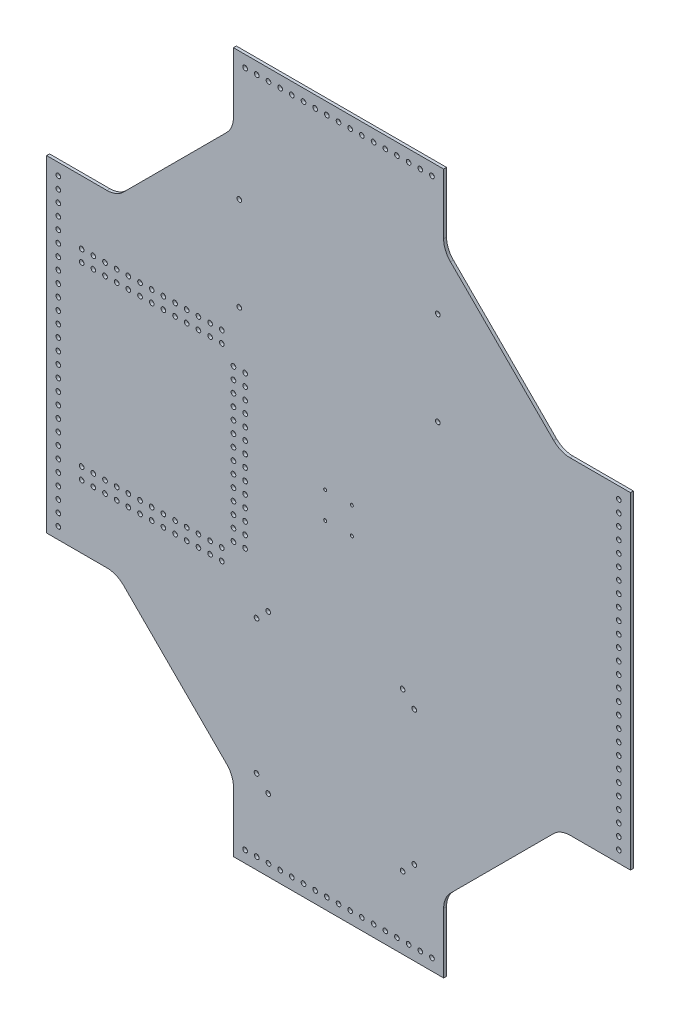
SolidWorks part; units mm, degrees
material "1060 Alloy"
ref_plane "Front Plane" through (0, 0, 0) normal (0, 0, 1) x (1, 0, 0)
ref_plane "Top Plane" through (0, 0, 0) normal (0, 1, 0) x (1, 0, 0)
ref_plane "Right Plane" through (0, 0, 0) normal (1, 0, 0) x (0, 0, -1)
sketch "Sketch1" plane through (0, 0, 0) normal (0, 0, 1) x (1, 0, 0)
  line L0 (-317.5, 177.8) -> (-317.5, -177.8)
  line L1 (-317.5, 381) -> (317.5, 381)
  line L2 (-317.5, 381) -> (-317.5, -381)
  line L3 (-317.5, -381) -> (317.5, -381)
  line L4 (317.5, 381) -> (317.5, -381)
  line L5 (-317.5, 381) -> (317.5, -381) construction
  line L6 (-317.5, -381) -> (317.5, 381) construction
  line L7 (317.5, 177.8) -> (317.5, -177.8)
  line L8 (-114.3, 381) -> (114.3, 381)
  line L9 (-114.3, -381) -> (114.3, -381)
  line L10 (-317.5, -177.8) -> (-241.3, -177.8)
  line L11 (-317.5, 177.8) -> (-241.3, 177.8)
  line L12 (-114.3, 381) -> (-114.3, 304.8)
  line L13 (114.3, 381) -> (114.3, 304.8)
  line L14 (317.5, 177.8) -> (241.3, 177.8)
  line L15 (317.5, -177.8) -> (241.3, -177.8)
  line L16 (114.3, -381) -> (114.3, -304.8)
  line L17 (-114.3, -381) -> (-114.3, -304.8)
  line L18 (-241.3, 177.8) -> (-114.3, 304.8)
  line L19 (114.3, 304.8) -> (241.3, 177.8)
  line L20 (114.3, -304.8) -> (241.3, -177.8)
  line L21 (-114.3, -304.8) -> (-241.3, -177.8)
  point P0 (0, 0)
  point P9 (-317.5, 0)
  point P12 (317.5, 0)
  point P15 (0, 381)
  point P18 (0, -381)
  dimension "D1" = 635
  dimension "D2" = 762
  dimension "D3" = 355.6
  dimension "D4" = 228.6
  dimension "D5" = 228.6
  dimension "D6" = 76.2
  dimension "D7" = 76.2
  dimension "D8" = 76.2
  dimension "D9" = 76.2
  dimension "D10" = 76.2
  dimension "D11" = 76.2
  dimension "D12" = 76.2
  dimension "D13" = 76.2
extrude "Boss-Extrude1" add sketch "Sketch1" along normal blind 3.175 contours L21 L17 L3 L16 L20 L15 L4 L14 L19 L13 L1 L12 L18 L11 L0 L10 region at (0, 0, 0)
sketch "Sketch2" plane through (0, 0, 3.175) normal (0, 0, 1) x (1, 0, 0)
  line L0 (-317.5, 177.8) -> (-317.5, -177.8) construction
  line L1 (-317.5, 177.8) -> (-241.3, 177.8) construction
  line L2 (-304.8, 177.8) -> (-304.8, -177.8) construction
  line L3 (-317.5, -177.8) -> (-241.3, -177.8) construction
  line L4 (0, 381) -> (0, -381) construction
  line L5 (-114.3, 381) -> (114.3, 381) construction
  line L6 (-114.3, -381) -> (114.3, -381) construction
  line L7 (-317.5, 0) -> (317.5, 0) construction
  line L8 (317.5, 177.8) -> (317.5, -177.8) construction
  line L9 (-114.3, -381) -> (-114.3, -304.8) construction
  line L10 (-114.3, -368.3) -> (114.3, -368.3) construction
  line L11 (114.3, -381) -> (114.3, -304.8) construction
  line L12 (-304.8, 165.1) -> (-292.1, 165.1) construction
  line L13 (-292.1, 165.1) -> (-292.1, -177.8) construction
  line L14 (317.5, 165.1) -> (272.8241, 165.1) construction
  line L15 (292.1, 177.8) -> (292.1, -177.8) construction
  line L16 (317.5, 177.8) -> (241.3, 177.8) construction
  line L17 (317.5, -177.8) -> (241.3, -177.8) construction
  line L18 (279.4, 177.8) -> (279.4, -177.8) construction
  line L19 (-101.6, -381) -> (-101.6, -331.9568) construction
  line L20 (-114.3, -342.9) -> (114.3, -342.9) construction
  line L21 (-114.3, -355.6) -> (114.3, -355.6) construction
  line L22 (-101.6, 381) -> (-101.6, 343.8859) construction
  line L23 (-114.3, 342.9) -> (114.3, 342.9) construction
  line L24 (-114.3, 381) -> (-114.3, 304.8) construction
  line L25 (114.3, 381) -> (114.3, 304.8) construction
  line L26 (-114.3, 355.6) -> (114.3, 355.6) construction
  circle A0 centre (-304.8, 165.1) radius 2.54
  circle A1 centre (-304.8, 152.4) radius 2.54
  circle A2 centre (-304.8, 139.7) radius 2.54
  circle A3 centre (-304.8, 127) radius 2.54
  circle A4 centre (-304.8, 114.3) radius 2.54
  circle A5 centre (-304.8, 101.6) radius 2.54
  circle A6 centre (-304.8, 88.9) radius 2.54
  circle A7 centre (-304.8, 76.2) radius 2.54
  circle A8 centre (-304.8, 63.5) radius 2.54
  circle A9 centre (-304.8, 50.8) radius 2.54
  circle A10 centre (-304.8, 38.1) radius 2.54
  circle A11 centre (-304.8, 25.4) radius 2.54
  circle A12 centre (-304.8, 12.7) radius 2.54
  circle A13 centre (-304.8, 0) radius 2.54
  circle A14 centre (-304.8, -12.7) radius 2.54
  circle A15 centre (-304.8, -25.4) radius 2.54
  circle A16 centre (-304.8, -38.1) radius 2.54
  circle A17 centre (-304.8, -50.8) radius 2.54
  circle A18 centre (-304.8, -63.5) radius 2.54
  circle A19 centre (-304.8, -76.2) radius 2.54
  circle A20 centre (-304.8, -88.9) radius 2.54
  circle A21 centre (-304.8, -101.6) radius 2.54
  circle A22 centre (-304.8, -114.3) radius 2.54
  circle A23 centre (-304.8, -127) radius 2.54
  circle A24 centre (-304.8, -139.7) radius 2.54
  circle A25 centre (-304.8, -152.4) radius 2.54
  circle A26 centre (-304.8, -165.1) radius 2.54
  circle A27 centre (304.8, -165.1) radius 2.54
  circle A28 centre (304.8, -152.4) radius 2.54
  circle A29 centre (304.8, -139.7) radius 2.54
  circle A30 centre (304.8, -127) radius 2.54
  circle A31 centre (304.8, -114.3) radius 2.54
  circle A32 centre (304.8, -101.6) radius 2.54
  circle A33 centre (304.8, -88.9) radius 2.54
  circle A34 centre (304.8, -76.2) radius 2.54
  circle A35 centre (304.8, -63.5) radius 2.54
  circle A36 centre (304.8, -50.8) radius 2.54
  circle A37 centre (304.8, -38.1) radius 2.54
  circle A38 centre (304.8, -25.4) radius 2.54
  circle A39 centre (304.8, -12.7) radius 2.54
  circle A40 centre (304.8, 0) radius 2.54
  circle A41 centre (304.8, 12.7) radius 2.54
  circle A42 centre (304.8, 25.4) radius 2.54
  circle A43 centre (304.8, 38.1) radius 2.54
  circle A44 centre (304.8, 50.8) radius 2.54
  circle A45 centre (304.8, 63.5) radius 2.54
  circle A46 centre (304.8, 76.2) radius 2.54
  circle A47 centre (304.8, 88.9) radius 2.54
  circle A48 centre (304.8, 101.6) radius 2.54
  circle A49 centre (304.8, 114.3) radius 2.54
  circle A50 centre (304.8, 127) radius 2.54
  circle A51 centre (304.8, 139.7) radius 2.54
  circle A52 centre (304.8, 152.4) radius 2.54
  circle A53 centre (304.8, 165.1) radius 2.54
  circle A54 centre (-101.6, -368.3) radius 2.54
  circle A55 centre (-88.9, -368.3) radius 2.54
  circle A56 centre (-76.2, -368.3) radius 2.54
  circle A57 centre (-63.5, -368.3) radius 2.54
  circle A58 centre (-50.8, -368.3) radius 2.54
  circle A59 centre (-38.1, -368.3) radius 2.54
  circle A60 centre (-25.4, -368.3) radius 2.54
  circle A61 centre (-12.7, -368.3) radius 2.54
  circle A62 centre (0, -368.3) radius 2.54
  circle A63 centre (12.7, -368.3) radius 2.54
  circle A64 centre (25.4, -368.3) radius 2.54
  circle A65 centre (38.1, -368.3) radius 2.54
  circle A66 centre (50.8, -368.3) radius 2.54
  circle A67 centre (63.5, -368.3) radius 2.54
  circle A68 centre (76.2, -368.3) radius 2.54
  circle A69 centre (88.9, -368.3) radius 2.54
  circle A70 centre (101.6, -368.3) radius 2.54
  circle A71 centre (101.6, 368.3) radius 2.54
  circle A72 centre (88.9, 368.3) radius 2.54
  circle A73 centre (76.2, 368.3) radius 2.54
  circle A74 centre (63.5, 368.3) radius 2.54
  circle A75 centre (50.8, 368.3) radius 2.54
  circle A76 centre (38.1, 368.3) radius 2.54
  circle A77 centre (25.4, 368.3) radius 2.54
  circle A78 centre (12.7, 368.3) radius 2.54
  circle A79 centre (0, 368.3) radius 2.54
  circle A80 centre (-12.7, 368.3) radius 2.54
  circle A81 centre (-25.4, 368.3) radius 2.54
  circle A82 centre (-38.1, 368.3) radius 2.54
  circle A83 centre (-50.8, 368.3) radius 2.54
  circle A84 centre (-63.5, 368.3) radius 2.54
  circle A85 centre (-76.2, 368.3) radius 2.54
  circle A86 centre (-88.9, 368.3) radius 2.54
  circle A87 centre (-101.6, 368.3) radius 2.54
  circle A115 centre (292.1, 165.1) radius 2.54
  circle A116 centre (279.4, 165.1) radius 2.54
  circle A117 centre (279.4, 152.4) radius 2.54
  circle A118 centre (292.1, 152.4) radius 2.54
  circle A119 centre (279.4, 139.7) radius 2.54
  circle A120 centre (292.1, 139.7) radius 2.54
  circle A121 centre (279.4, 127) radius 2.54
  circle A122 centre (292.1, 127) radius 2.54
  circle A123 centre (279.4, 114.3) radius 2.54
  circle A124 centre (292.1, 114.3) radius 2.54
  circle A125 centre (279.4, 101.6) radius 2.54
  circle A126 centre (292.1, 101.6) radius 2.54
  circle A127 centre (279.4, 88.9) radius 2.54
  circle A128 centre (292.1, 88.9) radius 2.54
  circle A129 centre (279.4, 76.2) radius 2.54
  circle A130 centre (292.1, 76.2) radius 2.54
  circle A131 centre (279.4, 63.5) radius 2.54
  circle A132 centre (292.1, 63.5) radius 2.54
  circle A133 centre (279.4, 50.8) radius 2.54
  circle A134 centre (292.1, 50.8) radius 2.54
  circle A135 centre (279.4, 38.1) radius 2.54
  circle A136 centre (292.1, 38.1) radius 2.54
  circle A137 centre (279.4, 25.4) radius 2.54
  circle A138 centre (292.1, 25.4) radius 2.54
  circle A139 centre (279.4, 12.7) radius 2.54
  circle A140 centre (292.1, 12.7) radius 2.54
  circle A141 centre (279.4, 0) radius 2.54
  circle A142 centre (292.1, 0) radius 2.54
  circle A143 centre (279.4, -12.7) radius 2.54
  circle A144 centre (292.1, -12.7) radius 2.54
  circle A145 centre (279.4, -25.4) radius 2.54
  circle A146 centre (292.1, -25.4) radius 2.54
  circle A147 centre (279.4, -38.1) radius 2.54
  circle A148 centre (292.1, -38.1) radius 2.54
  circle A149 centre (279.4, -50.8) radius 2.54
  circle A150 centre (292.1, -50.8) radius 2.54
  circle A151 centre (279.4, -63.5) radius 2.54
  circle A152 centre (292.1, -63.5) radius 2.54
  circle A153 centre (279.4, -76.2) radius 2.54
  circle A154 centre (292.1, -76.2) radius 2.54
  circle A155 centre (279.4, -88.9) radius 2.54
  circle A156 centre (292.1, -88.9) radius 2.54
  circle A157 centre (279.4, -101.6) radius 2.54
  circle A158 centre (292.1, -101.6) radius 2.54
  circle A159 centre (279.4, -114.3) radius 2.54
  circle A160 centre (292.1, -114.3) radius 2.54
  circle A161 centre (279.4, -127) radius 2.54
  circle A162 centre (292.1, -127) radius 2.54
  circle A163 centre (279.4, -139.7) radius 2.54
  circle A164 centre (292.1, -139.7) radius 2.54
  circle A165 centre (279.4, -152.4) radius 2.54
  circle A166 centre (292.1, -152.4) radius 2.54
  circle A167 centre (279.4, -165.1) radius 2.54
  circle A168 centre (292.1, -165.1) radius 2.54
  circle A169 centre (-101.6, -355.6) radius 2.54
  circle A170 centre (-101.6, -342.9) radius 2.54
  circle A171 centre (-88.9, -342.9) radius 2.54
  circle A172 centre (-88.9, -355.6) radius 2.54
  circle A173 centre (-76.2, -342.9) radius 2.54
  circle A174 centre (-76.2, -355.6) radius 2.54
  circle A175 centre (-63.5, -342.9) radius 2.54
  circle A176 centre (-63.5, -355.6) radius 2.54
  circle A177 centre (-50.8, -342.9) radius 2.54
  circle A178 centre (-50.8, -355.6) radius 2.54
  circle A179 centre (-38.1, -342.9) radius 2.54
  circle A180 centre (-38.1, -355.6) radius 2.54
  circle A181 centre (-25.4, -342.9) radius 2.54
  circle A182 centre (-25.4, -355.6) radius 2.54
  circle A183 centre (-12.7, -342.9) radius 2.54
  circle A184 centre (-12.7, -355.6) radius 2.54
  circle A185 centre (0, -342.9) radius 2.54
  circle A186 centre (0, -355.6) radius 2.54
  circle A187 centre (12.7, -342.9) radius 2.54
  circle A188 centre (12.7, -355.6) radius 2.54
  circle A189 centre (25.4, -342.9) radius 2.54
  circle A190 centre (25.4, -355.6) radius 2.54
  circle A191 centre (38.1, -342.9) radius 2.54
  circle A192 centre (38.1, -355.6) radius 2.54
  circle A193 centre (50.8, -342.9) radius 2.54
  circle A194 centre (50.8, -355.6) radius 2.54
  circle A195 centre (63.5, -342.9) radius 2.54
  circle A196 centre (63.5, -355.6) radius 2.54
  circle A197 centre (76.2, -342.9) radius 2.54
  circle A198 centre (76.2, -355.6) radius 2.54
  circle A199 centre (88.9, -342.9) radius 2.54
  circle A200 centre (88.9, -355.6) radius 2.54
  circle A201 centre (101.6, -342.9) radius 2.54
  circle A202 centre (101.6, -355.6) radius 2.54
  circle A203 centre (-101.6, 355.6) radius 2.54
  circle A204 centre (-101.6, 342.9) radius 2.54
  circle A205 centre (-88.9, 342.9) radius 2.54
  circle A206 centre (-88.9, 355.6) radius 2.54
  circle A207 centre (-76.2, 342.9) radius 2.54
  circle A208 centre (-76.2, 355.6) radius 2.54
  circle A209 centre (-63.5, 342.9) radius 2.54
  circle A210 centre (-63.5, 355.6) radius 2.54
  circle A211 centre (-50.8, 342.9) radius 2.54
  circle A212 centre (-50.8, 355.6) radius 2.54
  circle A213 centre (-38.1, 342.9) radius 2.54
  circle A214 centre (-38.1, 355.6) radius 2.54
  circle A215 centre (-25.4, 342.9) radius 2.54
  circle A216 centre (-25.4, 355.6) radius 2.54
  circle A217 centre (-12.7, 342.9) radius 2.54
  circle A218 centre (-12.7, 355.6) radius 2.54
  circle A219 centre (0, 342.9) radius 2.54
  circle A220 centre (0, 355.6) radius 2.54
  circle A221 centre (12.7, 342.9) radius 2.54
  circle A222 centre (12.7, 355.6) radius 2.54
  circle A223 centre (25.4, 342.9) radius 2.54
  circle A224 centre (25.4, 355.6) radius 2.54
  circle A225 centre (38.1, 342.9) radius 2.54
  circle A226 centre (38.1, 355.6) radius 2.54
  circle A227 centre (50.8, 342.9) radius 2.54
  circle A228 centre (50.8, 355.6) radius 2.54
  circle A229 centre (63.5, 342.9) radius 2.54
  circle A230 centre (63.5, 355.6) radius 2.54
  circle A231 centre (76.2, 342.9) radius 2.54
  circle A232 centre (76.2, 355.6) radius 2.54
  circle A233 centre (88.9, 342.9) radius 2.54
  circle A234 centre (88.9, 355.6) radius 2.54
  circle A235 centre (101.6, 342.9) radius 2.54
  circle A236 centre (101.6, 355.6) radius 2.54
  dimension "D1" = 5.08
  dimension "D5" = 5.08
  dimension "D2" = 12.7
  dimension "D3" = 12.7
  dimension "D6" = 12.7
  dimension "D7" = 12.7
  dimension "D9" = 12.7
  dimension "D4" = 27
  dimension "D8" = 17
  dimension "D11" = 3
  dimension "D12" = 27
  dimension "D13" = 3
  dimension "D14" = 17
  dimension "D15" = 3
  dimension "D16" = 17
extrude "Cut-Extrude2" cut sketch "Sketch2" against normal blind 3.175 contours A87 | A86 | A85 | A84 | A83 | A82 | A80 | A81 | A79 | A78 | A77 | A76 | A75 | A74 | A73 | A72 | A71 | A53 | A52 | A51 | A50 | A49 | A48 | A47 | A46 | A45 | A44 | A43 | A42 | A41 | A40 | A39 | A38 | A37 | A36 | A35 | A34 | A33 | A32 | A31 | A30 | A29 | A28 | A27 | A70 | A69 | A68 | A67 | A66 | A65 | A64 | A63 | A62 | A61 | A60 | A59 | A58 | A56 | A57 | A55 | A54 | A26 | A25 | A24 | A23 | A22 | A21 | A20 | A19 | A18 | A17 | A16 | A15 | A14 | A13 | A12 | A11 | A10 | A9 | A8 | A7 | A0 | A1 | A2 | A3 | A4 | A5 | A6
sketch "Sketch3" plane through (0, 0, 3.175) normal (0, 0, 1) x (1, 0, 0)
  line L0 (-317.5, 177.8) -> (-317.5, -177.8) construction
  line L1 (-14.478, 14.478) -> (14.478, 14.478)
  line L2 (-14.478, 14.478) -> (-14.478, -14.478)
  line L3 (-14.478, -14.478) -> (14.478, -14.478)
  line L4 (14.478, 14.478) -> (14.478, -14.478)
  line L5 (-14.478, 14.478) -> (14.478, -14.478) construction
  line L6 (-14.478, -14.478) -> (14.478, 14.478) construction
  line L7 (-107.95, 241.3) -> (107.95, 241.3)
  line L8 (-107.95, 241.3) -> (-107.95, 139.7)
  line L9 (-107.95, 139.7) -> (107.95, 139.7)
  line L10 (107.95, 241.3) -> (107.95, 139.7)
  line L11 (-107.95, 241.3) -> (107.95, 139.7) construction
  line L12 (-107.95, 139.7) -> (107.95, 241.3) construction
  line L14 (-114.3, 381) -> (114.3, 381) construction
  circle A0 centre (-14.478, 14.478) radius 1.651
  circle A1 centre (14.478, 14.478) radius 1.651
  circle A2 centre (14.478, -14.478) radius 1.651
  circle A3 centre (-14.478, -14.478) radius 1.651
  circle A4 centre (-107.95, 241.3) radius 2.54
  circle A5 centre (107.95, 241.3) radius 2.54
  circle A6 centre (107.95, 139.7) radius 2.54
  circle A7 centre (-107.95, 139.7) radius 2.54
  point P0 (0, 0)
  point P10 (0, 190.5)
  dimension "D6" = 5.08
  dimension "D7" = 5.08
  dimension "D8" = 5.08
  dimension "D9" = 5.08
  dimension "D11" = 3.302
  dimension "D12" = 3.302
  dimension "D13" = 3.302
  dimension "D14" = 3.302
  dimension "D1" = 28.956
  dimension "D2" = 28.956
  dimension "D3" = 215.9
  dimension "D4" = 101.6
  dimension "D5" = 209.55
  dimension "D10" = 241.3
extrude "Cut-Extrude3" cut sketch "Sketch3" against normal blind 3.175 contours L10 A5 L7 | L8 A7 L9 | L7 A4 L8 | L8 A4 L7 | L9 A7 L8 | L9 A6 L10 | L10 A6 L9 | L7 A5 L10 | A6 | A0 | A1 | A2 | A3 region at (-108.3093, 241.6593, 3.175) region at (-106.872, 240.222, 3.175) region at (108.3093, 241.6593, 3.175) region at (106.872, 240.222, 3.175) region at (-106.872, 140.778, 3.175) region at (-108.3093, 139.3407, 3.175) region at (108.3093, 139.3407, 3.175) region at (106.872, 140.778, 3.175)
sketch "Sketch4" plane through (0, 0, 3.175) normal (0, 0, 1) x (1, 0, 0)
  line L0 (-292.1, 177.8) -> (-292.1, -177.8) construction
  line L1 (-317.5, 177.8) -> (-241.3, 177.8) construction
  line L2 (-317.5, -177.8) -> (-241.3, -177.8) construction
  line L3 (-317.5, 177.8) -> (-317.5, -177.8) construction
  line L4 (-292.1, 83.439) -> (-292.1, 96.139) construction
  line L5 (-292.1, 83.439) -> (-110.998, 83.439)
  line L7 (-292.1, -83.439) -> (-110.998, -83.439)
  line L8 (-110.998, 83.439) -> (-110.998, -83.439)
  line L9 (-292.1, 96.139) -> (-98.298, 96.139) construction
  line L10 (-98.298, 96.139) -> (-98.298, -96.139) construction
  line L11 (-98.298, -96.139) -> (-292.1, -96.139) construction
  line L12 (-292.1, 96.139) -> (-279.4, 96.139) construction
  line L13 (-317.5, 0) -> (317.5, 0) construction
  line L14 (317.5, 177.8) -> (317.5, -177.8) construction
  line L15 (-292.1, 108.839) -> (-85.598, 108.839) construction
  line L16 (-85.598, 108.839) -> (-85.598, -108.839) construction
  line L17 (-85.598, -108.839) -> (-292.1, -108.839) construction
  line L18 (-114.3, 96.139) -> (-114.3, -96.139) construction
  line L19 (-114.3, -71.501) -> (-114.3, -84.201) construction
  line L20 (-101.6, -86.741) -> (-101.6, 96.139) construction
  line L21 (-114.3, -84.201) -> (-101.6, -84.201) construction
  circle A0 centre (-279.4, 96.139) radius 2.54
  circle A1 centre (-266.7, 96.139) radius 2.54
  circle A2 centre (-254, 96.139) radius 2.54
  circle A3 centre (-241.3, 96.139) radius 2.54
  circle A4 centre (-228.6, 96.139) radius 2.54
  circle A5 centre (-215.9, 96.139) radius 2.54
  circle A6 centre (-203.2, 96.139) radius 2.54
  circle A7 centre (-190.5, 96.139) radius 2.54
  circle A8 centre (-177.8, 96.139) radius 2.54
  circle A9 centre (-165.1, 96.139) radius 2.54
  circle A10 centre (-152.4, 96.139) radius 2.54
  circle A11 centre (-139.7, 96.139) radius 2.54
  circle A12 centre (-127, 96.139) radius 2.54
  circle A15 centre (-127, -96.139) radius 2.54
  circle A16 centre (-139.7, -96.139) radius 2.54
  circle A17 centre (-152.4, -96.139) radius 2.54
  circle A18 centre (-165.1, -96.139) radius 2.54
  circle A19 centre (-177.8, -96.139) radius 2.54
  circle A20 centre (-190.5, -96.139) radius 2.54
  circle A21 centre (-203.2, -96.139) radius 2.54
  circle A22 centre (-215.9, -96.139) radius 2.54
  circle A23 centre (-228.6, -96.139) radius 2.54
  circle A24 centre (-241.3, -96.139) radius 2.54
  circle A25 centre (-254, -96.139) radius 2.54
  circle A26 centre (-266.7, -96.139) radius 2.54
  circle A27 centre (-279.4, -96.139) radius 2.54
  circle A44 centre (-279.4, -108.839) radius 2.54
  circle A48 centre (-279.4, 108.839) radius 2.54
  circle A49 centre (-266.7, 108.839) radius 2.54
  circle A50 centre (-254, 108.839) radius 2.54
  circle A51 centre (-241.3, 108.839) radius 2.54
  circle A52 centre (-228.6, 108.839) radius 2.54
  circle A53 centre (-215.9, 108.839) radius 2.54
  circle A54 centre (-203.2, 108.839) radius 2.54
  circle A55 centre (-190.5, 108.839) radius 2.54
  circle A56 centre (-177.8, 108.839) radius 2.54
  circle A57 centre (-165.1, 108.839) radius 2.54
  circle A58 centre (-152.4, 108.839) radius 2.54
  circle A59 centre (-139.7, 108.839) radius 2.54
  circle A60 centre (-127, 108.839) radius 2.54
  circle A78 centre (-127, -108.839) radius 2.54
  circle A79 centre (-139.7, -108.839) radius 2.54
  circle A80 centre (-152.4, -108.839) radius 2.54
  circle A81 centre (-165.1, -108.839) radius 2.54
  circle A82 centre (-177.8, -108.839) radius 2.54
  circle A83 centre (-190.5, -108.839) radius 2.54
  circle A84 centre (-203.2, -108.839) radius 2.54
  circle A85 centre (-215.9, -108.839) radius 2.54
  circle A86 centre (-228.6, -108.839) radius 2.54
  circle A87 centre (-241.3, -108.839) radius 2.54
  circle A88 centre (-254, -108.839) radius 2.54
  circle A89 centre (-266.7, -108.839) radius 2.54
  circle A90 centre (-114.3, 108.839) radius 2.54 [skipped]
  circle A91 centre (-114.3, 80.899) radius 2.54
  circle A104 centre (-114.3, 68.199) radius 2.54
  circle A106 centre (-101.6, -84.201) radius 2.54
  circle A107 centre (-101.6, -71.501) radius 2.54
  circle A108 centre (-101.6, -58.801) radius 2.54
  circle A109 centre (-101.6, -46.101) radius 2.54
  circle A110 centre (-101.6, -33.401) radius 2.54
  circle A111 centre (-101.6, -20.701) radius 2.54
  circle A112 centre (-101.6, -8.001) radius 2.54
  circle A113 centre (-101.6, 4.699) radius 2.54
  circle A114 centre (-101.6, 17.399) radius 2.54
  circle A115 centre (-101.6, 30.099) radius 2.54
  circle A116 centre (-101.6, 42.799) radius 2.54
  circle A117 centre (-101.6, 55.499) radius 2.54
  circle A118 centre (-101.6, 68.199) radius 2.54
  circle A119 centre (-101.6, 80.899) radius 2.54
  circle A120 centre (-114.3, 55.499) radius 2.54
  circle A121 centre (-114.3, 42.799) radius 2.54
  circle A122 centre (-114.3, 30.099) radius 2.54
  circle A123 centre (-114.3, 17.399) radius 2.54
  circle A124 centre (-114.3, 4.699) radius 2.54
  circle A125 centre (-114.3, -8.001) radius 2.54
  circle A126 centre (-114.3, -20.701) radius 2.54
  circle A127 centre (-114.3, -33.401) radius 2.54
  circle A128 centre (-114.3, -46.101) radius 2.54
  circle A129 centre (-114.3, -58.801) radius 2.54
  circle A130 centre (-114.3, -71.501) radius 2.54
  circle A131 centre (-114.3, -84.201) radius 2.54
  dimension "D9" = 5.08
  dimension "D14" = 12.7
  dimension "D17" = 14
  dimension "D11" = 14
  dimension "D1" = 25.4
  dimension "D2" = 181.102
  dimension "D3" = 12.7
  dimension "D4" = 94.361
  dimension "D5" = 12.7
  dimension "D6" = 12.7
  dimension "D7" = 12.7
  dimension "D8" = 12.7
  dimension "D15" = 12.7
  dimension "D16" = 12.7
  dimension "D10" = 14
extrude "Cut-Extrude5" cut sketch "Sketch4" against normal blind 3.175 contours A44 | A26 | A25 | A88 | A89 | A24 | A87 | A86 | A23 | A22 | A21 | A20 | A19 | A18 | A17 | A16 | A15 | A119 | A78 | A79 | A80 | A81 | A82 | A83 | A84 | A85 | A60 | A59 | A58 | A57 | A56 | A55 | A54 | A53 | A5 | A6 | A7 | A8 | A9 | A10 | A12 | A0 | A48 | A49 | A50 | A51 | A52 | A4 | A2 | A1 | A89 | A78 | A3 | A11 | A91 | A104 | A118 | A120 | A117 | A121 | A116 | A122 | A115 | A123 | A114 | A124 | A113 | A125 | A112 | A111 | A126 | A131 | A106 | A107 | A130 | A108 | A129 | A128 | A109 | A110 | A127 | A27 region at (-279.4, 96.139, 3.175) region at (-266.7, 96.139, 3.175) region at (-254, 96.139, 3.175) region at (-228.6, 96.139, 3.175) region at (-215.9, 96.139, 3.175) region at (-203.2, 96.139, 3.175) region at (-190.5, 96.139, 3.175) region at (-177.8, 96.139, 3.175) region at (-165.1, 96.139, 3.175) region at (-152.4, 96.139, 3.175) region at (-127, 96.139, 3.175) region at (-127, -96.139, 3.175) region at (-139.7, -96.139, 3.175) region at (-152.4, -96.139, 3.175) region at (-165.1, -96.139, 3.175) region at (-177.8, -96.139, 3.175) region at (-190.5, -96.139, 3.175) region at (-203.2, -96.139, 3.175) region at (-215.9, -96.139, 3.175) region at (-228.6, -96.139, 3.175) region at (-241.3, -96.139, 3.175) region at (-254, -96.139, 3.175) region at (-266.7, -96.139, 3.175) region at (-279.4, -108.839, 3.175) region at (-279.4, 108.839, 3.175) region at (-266.7, 108.839, 3.175) region at (-254, 108.839, 3.175) region at (-241.3, 108.839, 3.175) region at (-228.6, 108.839, 3.175) region at (-215.9, 108.839, 3.175) region at (-203.2, 108.839, 3.175) region at (-190.5, 108.839, 3.175) region at (-177.8, 108.839, 3.175) region at (-165.1, 108.839, 3.175) region at (-152.4, 108.839, 3.175) region at (-139.7, 108.839, 3.175) region at (-127, 108.839, 3.175) region at (-127, -108.839, 3.175) region at (-139.7, -108.839, 3.175) region at (-152.4, -108.839, 3.175) region at (-165.1, -108.839, 3.175) region at (-177.8, -108.839, 3.175) region at (-190.5, -108.839, 3.175) region at (-203.2, -108.839, 3.175) region at (-215.9, -108.839, 3.175) region at (-228.6, -108.839, 3.175) region at (-241.3, -108.839, 3.175) region at (-254, -108.839, 3.175) region at (-266.7, -108.839, 3.175) region at (-101.6, 80.899, 3.175)
sketch "Sketch5" plane through (0, 0, 3.175) normal (0, 0, 1) x (1, 0, 0)
  line L0 (-76.4928, -143.819) -> (-76.4928, -131.119) construction
  line L1 (-76.4928, -143.819) -> (69.6588, -143.819) construction
  line L2 (-76.4928, -143.819) -> (-76.4928, -289.9706) construction
  line L3 (-76.4928, -289.9706) -> (69.6588, -289.9706) construction
  line L4 (69.6588, -143.819) -> (69.6588, -289.9706) construction
  line L5 (-76.4928, -143.819) -> (69.6588, -289.9706) construction
  line L6 (-76.4928, -289.9706) -> (69.6588, -143.819) construction
  line L7 (-76.4928, -143.819) -> (-89.1928, -143.819) construction
  line L8 (82.3588, -143.819) -> (69.6588, -143.819) construction
  line L9 (69.6588, -143.819) -> (69.6588, -131.119) construction
  line L10 (69.6588, -289.9706) -> (82.3588, -289.9706) construction
  line L11 (-76.4928, -289.9706) -> (-89.1928, -289.9706) construction
  line L12 (-76.4928, -289.9706) -> (-76.4928, -302.6706) construction
  line L13 (69.6588, -289.9706) -> (69.6588, -302.6706) construction
  circle A0 centre (-76.4928, -131.119) radius 2.54
  circle A1 centre (-89.1928, -143.819) radius 2.54
  circle A2 centre (69.6588, -131.119) radius 2.54
  circle A3 centre (82.3588, -143.819) radius 2.54
  circle A4 centre (82.3588, -289.9706) radius 2.54
  circle A5 centre (69.6588, -302.6706) radius 2.54
  circle A6 centre (-76.4928, -302.6706) radius 2.54
  circle A7 centre (-89.1928, -289.9706) radius 2.54
  point P0 (-3.417, -216.8948)
  dimension "D5" = 12.7
  dimension "D1" = 146.1516
  dimension "D2" = 146.1516
  dimension "D3" = 12.7
  dimension "D4" = 12.7
  dimension "D6" = 12.7
  dimension "D7" = 12.7
  dimension "D8" = 12.7
  dimension "D9" = 12.7
  dimension "D10" = 12.7
extrude "Cut-Extrude7" cut sketch "Sketch5" against normal blind 3.175 contours A7 | A6 | A5 | A4 | A3 | A2 | A0 | A1
fillet "Fillet1" radius 25.4 1 edges at (-241.3, -177.8, 1.5875)
fillet "Fillet2" radius 25.4 1 edges at (-114.3, -304.8, 1.5875)
fillet "Fillet3" radius 25.4 2 edges at (114.3, -304.8, 1.5875) (241.3, -177.8, 1.5875)
fillet "Fillet4" radius 25.4 2 edges at (114.3, 304.8, 1.5875) (241.3, 177.8, 1.5875)
fillet "Fillet5" radius 25.4 2 edges at (-241.3, 177.8, 1.5875) (-114.3, 304.8, 1.5875)
sketch "Sketch7" plane through (0, 0, 3.175) normal (0, 0, 1) x (1, 0, 0)
  line L0 (317.5, -177.8) -> (251.821, -177.8) construction
  line L1 (-114.3, 247.65) -> (-101.6, 247.65)
  line L2 (-114.3, 247.65) -> (-114.3, 234.95)
  line L3 (-114.3, 234.95) -> (-101.6, 234.95)
  line L4 (-101.6, 247.65) -> (-101.6, 234.95)
  line L5 (-114.3, 247.65) -> (-101.6, 234.95) construction
  line L6 (-114.3, 234.95) -> (-101.6, 247.65) construction
  line L7 (101.6, 247.65) -> (114.3, 247.65)
  line L8 (101.6, 247.65) -> (101.6, 234.95)
  line L9 (101.6, 234.95) -> (114.3, 234.95)
  line L10 (114.3, 247.65) -> (114.3, 234.95)
  line L11 (101.6, 247.65) -> (114.3, 234.95) construction
  line L12 (101.6, 234.95) -> (114.3, 247.65) construction
  line L13 (101.6, 146.05) -> (114.3, 146.05)
  line L14 (101.6, 146.05) -> (101.6, 133.35)
  line L15 (101.6, 133.35) -> (114.3, 133.35)
  line L16 (114.3, 146.05) -> (114.3, 133.35)
  line L17 (101.6, 146.05) -> (114.3, 133.35) construction
  line L18 (101.6, 133.35) -> (114.3, 146.05) construction
  line L19 (-114.3, 146.0909) -> (-101.6, 146.0909)
  line L20 (-114.3, 146.0909) -> (-114.3, 133.3091)
  line L21 (-114.3, 133.3091) -> (-101.6, 133.3091)
  line L22 (-101.6, 146.0909) -> (-101.6, 133.3091)
  line L23 (-114.3, 146.0909) -> (-101.6, 133.3091) construction
  line L24 (-114.3, 133.3091) -> (-101.6, 146.0909) construction
  line L25 (-17.653, 17.653) -> (-11.303, 17.653)
  line L26 (-17.653, 17.653) -> (-17.653, 11.303)
  line L27 (-17.653, 11.303) -> (-11.303, 11.303)
  line L28 (-11.303, 17.653) -> (-11.303, 11.303)
  line L29 (-17.653, 17.653) -> (-11.303, 11.303) construction
  line L30 (-17.653, 11.303) -> (-11.303, 17.653) construction
  line L31 (11.303, 17.653) -> (17.653, 17.653)
  line L32 (11.303, 17.653) -> (11.303, 11.303)
  line L33 (11.303, 11.303) -> (17.653, 11.303)
  line L34 (17.653, 17.653) -> (17.653, 11.303)
  line L35 (11.303, 17.653) -> (17.653, 11.303) construction
  line L36 (11.303, 11.303) -> (17.653, 17.653) construction
  line L37 (11.303, -11.303) -> (17.653, -11.303)
  line L38 (11.303, -11.303) -> (11.303, -17.653)
  line L39 (11.303, -17.653) -> (17.653, -17.653)
  line L40 (17.653, -11.303) -> (17.653, -17.653)
  line L41 (11.303, -11.303) -> (17.653, -17.653) construction
  line L42 (11.303, -17.653) -> (17.653, -11.303) construction
  line L43 (-17.653, -11.303) -> (-11.303, -11.303)
  line L44 (-17.653, -11.303) -> (-17.653, -17.653)
  line L45 (-17.653, -17.653) -> (-11.303, -17.653)
  line L46 (-11.303, -11.303) -> (-11.303, -17.653)
  line L47 (-17.653, -11.303) -> (-11.303, -17.653) construction
  line L48 (-17.653, -17.653) -> (-11.303, -11.303) construction
  line L49 (-95.4935, -283.7717) -> (-70.0935, -283.7717)
  line L50 (-95.4935, -283.7717) -> (-95.4935, -309.1717)
  line L51 (-95.4935, -309.1717) -> (-70.0935, -309.1717)
  line L52 (-70.0935, -283.7717) -> (-70.0935, -309.1717)
  line L53 (62.0918, -283.7717) -> (87.4918, -283.7717)
  line L54 (62.0918, -283.7717) -> (62.0918, -309.1717)
  line L55 (62.0918, -309.1717) -> (87.4918, -309.1717)
  line L56 (87.4918, -283.7717) -> (87.4918, -309.1717)
  line L57 (62.9487, -124.8997) -> (88.3487, -124.8997)
  line L58 (62.9487, -124.8997) -> (62.9487, -150.2997)
  line L59 (62.9487, -150.2997) -> (88.3487, -150.2997)
  line L60 (88.3487, -124.8997) -> (88.3487, -150.2997)
  line L61 (-95.4935, -124.8997) -> (-70.0935, -124.8997)
  line L62 (-95.4935, -124.8997) -> (-95.4935, -150.2997)
  line L63 (-95.4935, -150.2997) -> (-70.0935, -150.2997)
  line L64 (-70.0935, -124.8997) -> (-70.0935, -150.2997)
  line L77 (-317.5, 177.8) -> (-292.1, 177.8)
  line L78 (-317.5, 177.8) -> (-317.5, -177.8)
  line L79 (-317.5, -177.8) -> (-292.1, -177.8)
  line L80 (-292.1, 177.8) -> (-292.1, -177.8)
  line L81 (317.5, 177.8) -> (292.1, 177.8)
  line L82 (317.5, 177.8) -> (317.5, -177.8)
  line L83 (317.5, -177.8) -> (292.1, -177.8)
  line L84 (292.1, 177.8) -> (292.1, -177.8)
  line L85 (114.3, 381) -> (114.3, 315.321) construction
  line L86 (-114.3, 381) -> (114.3, 381)
  line L87 (-114.3, 381) -> (-114.3, 355.6)
  line L88 (-114.3, 355.6) -> (114.3, 355.6)
  line L89 (114.3, 381) -> (114.3, 355.6)
  line L90 (114.3, -381) -> (114.3, -315.321) construction
  line L91 (-114.3, -381) -> (114.3, -381)
  line L92 (-114.3, -381) -> (-114.3, -355.6)
  line L93 (-114.3, -355.6) -> (114.3, -355.6)
  line L94 (114.3, -381) -> (114.3, -355.6)
  line L96 (-292.1, -90.4018) -> (-95.4935, -90.4018)
  line L97 (-292.1, -90.4018) -> (-292.1, -115.8018)
  line L98 (-292.1, -115.8018) -> (-95.4935, -115.8018)
  line L99 (-95.4935, -90.4018) -> (-95.4935, -115.8018)
  line L100 (-292.1, 114.5889) -> (-95.4935, 114.5889)
  line L101 (-292.1, 114.5889) -> (-292.1, 89.1889)
  line L102 (-292.1, 89.1889) -> (-95.4935, 89.1889)
  line L103 (-95.4935, 114.5889) -> (-95.4935, 89.1889)
  line L104 (-95.4935, 89.1889) -> (-120.8935, 89.1889)
  line L105 (-95.4935, 89.1889) -> (-95.4935, -90.4018)
  line L106 (-95.4935, -90.4018) -> (-120.8935, -90.4018)
  line L107 (-120.8935, 89.1889) -> (-120.8935, -90.4018)
  point P0 (-107.95, 241.3)
  point P6 (107.95, 241.3)
  point P12 (107.95, 139.7)
  point P18 (-107.95, 139.7)
  point P24 (-14.478, 14.478)
  point P30 (14.478, 14.478)
  point P36 (14.478, -14.478)
  point P42 (-14.478, -14.478)
  dimension "D1" = 12.7
  dimension "D2" = 12.7
  dimension "D3" = 12.7
  dimension "D4" = 12.7
  dimension "D5" = 12.7
  dimension "D6" = 12.7
  dimension "D7" = 12.7
  dimension "D8" = 12.7818
  dimension "D9" = 6.35
  dimension "D10" = 6.35
  dimension "D11" = 6.35
  dimension "D12" = 6.35
  dimension "D13" = 6.35
  dimension "D14" = 6.35
  dimension "D15" = 6.35
  dimension "D16" = 6.35
  dimension "D17" = 25.4
  dimension "D18" = 25.4
  dimension "D19" = 25.4
  dimension "D20" = 25.4
  dimension "D21" = 25.4
  dimension "D22" = 25.4
  dimension "D23" = 25.4
  dimension "D24" = 25.4
  dimension "D25" = 25.4
  dimension "D26" = 25.4
  dimension "D27" = 25.4
  dimension "D28" = 25.4
  dimension "D29" = 25.4
